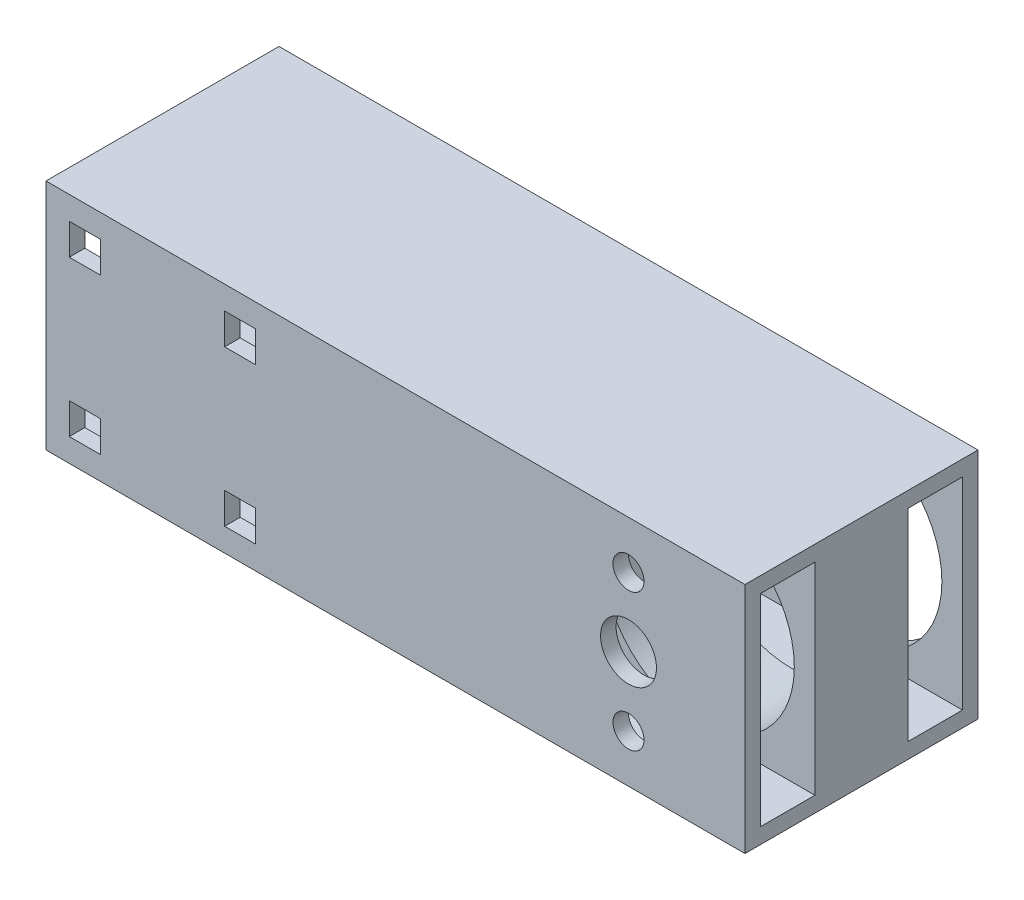
SolidWorks part; units mm, degrees
material "PLA 15%"
ref_plane "Front Plane" through (0, 0, 0) normal (0, 0, 1) x (1, 0, 0)
ref_plane "Top Plane" through (0, 0, 0) normal (0, 1, 0) x (1, 0, 0)
ref_plane "Right Plane" through (0, 0, 0) normal (1, 0, 0) x (0, 0, -1)
sketch "Sketch1" plane through (0, 0, 0) normal (1, 0, 0) x (0, 0, -1)
  line L1 (-15, -15) -> (15, -15)
  line L2 (-15, -15) -> (-15, 15)
  line L3 (-15, 15) -> (15, 15)
  line L4 (15, -15) -> (15, 15)
  line L5 (-15, -15) -> (15, 15) construction
  line L6 (-15, 15) -> (15, -15) construction
  line L11 (-5.1844, 5.1844) -> (5.1844, -5.1844) construction
  line L12 (-5.1844, -5.1844) -> (5.1844, 5.1844) construction
  line L13 (-13, 13) -> (-6, 13)
  line L14 (-13, 13) -> (-13, -13)
  line L15 (-13, -13) -> (-6, -13)
  line L16 (-6, 13) -> (-6, -13)
  line L17 (13, 13) -> (6, 13)
  line L18 (13, 13) -> (13, -13)
  line L19 (13, -13) -> (6, -13)
  line L20 (6, 13) -> (6, -13)
  point P0 (0, 0)
  point P7 (0, 0)
  dimension "D1" = 30
  dimension "D2" = 30
  dimension "D3" = 2
  dimension "D4" = 7
  dimension "D5" = 2
  dimension "D6" = 7
  dimension "D7" = 2
  dimension "D8" = 2
extrude "Boss-Extrude3" add sketch "Sketch1" along normal blind 90
sketch "Sketch6" plane through (0, 0, -15) normal (0, 0, -1) x (-1, 0, 0)
  line L0 (-90, -15) -> (-90, 15) construction
  circle A0 centre (-75, 0) radius 12.35
  dimension "D2" = 24.7
  dimension "D1" = 15
extrude "Cut-Extrude5" cut sketch "Sketch6" against normal blind 23
sketch "Sketch8" plane through (0, 0, 15) normal (0, 0, 1) x (1, 0, 0)
  line L0 (90, 15) -> (90, -15) construction
  circle A0 centre (75, 0) radius 3.6
  circle A1 centre (75, 8.85) radius 2
  circle A2 centre (75, -8.85) radius 2
  dimension "D2" = 7.2
  dimension "D5" = 4
  dimension "D6" = 4
  dimension "D1" = 15
  dimension "D3" = 8.85
  dimension "D4" = 8.85
extrude "Cut-Extrude6" cut sketch "Sketch8" against normal blind 17
sketch "Sketch9" plane through (0, 0, 0) normal (-1, 0, 0) x (0, 0, 1)
  line L0 (-6, 13) -> (6, 13)
  line L1 (-6, -13) -> (6, -13)
  line L2 (-6, 13) -> (-6, -13)
  line L3 (6, 13) -> (6, -13)
extrude "Cut-Extrude7" cut sketch "Sketch9" against normal blind 59
sketch "Sketch10" plane through (0, 0, -15) normal (0, 0, -1) x (-1, 0, 0)
  line L0 (0, 15) -> (-30, 15)
  line L1 (-90, 15) -> (0, 15) construction
  line L2 (-30, 15) -> (-30, -15)
  line L3 (-90, -15) -> (0, -15) construction
  line L4 (-30, -15) -> (0, -15)
  line L5 (-25, 10) -> (0, 10)
  line L6 (0, -15) -> (0, 15) construction
  line L7 (-25, 10) -> (-25, -15)
  line L9 (-3, 8) -> (-7, 8)
  line L10 (-3, 8) -> (-3, 12)
  line L11 (-3, 12) -> (-7, 12)
  line L12 (-7, 8) -> (-7, 12)
  line L13 (-3, 8) -> (-7, 12) construction
  line L14 (-3, 12) -> (-7, 8) construction
  line L15 (-27, 8) -> (-23, 8)
  line L16 (-27, 8) -> (-27, 12)
  line L17 (-27, 12) -> (-23, 12)
  line L18 (-23, 8) -> (-23, 12)
  line L19 (-27, 8) -> (-23, 12) construction
  line L20 (-27, 12) -> (-23, 8) construction
  line L22 (-27, -12) -> (-23, -12)
  line L23 (-27, -12) -> (-27, -8)
  line L24 (-27, -8) -> (-23, -8)
  line L25 (-23, -12) -> (-23, -8)
  line L26 (-27, -12) -> (-23, -8) construction
  line L27 (-27, -8) -> (-23, -12) construction
  line L28 (-3, -12) -> (-7, -12)
  line L29 (-3, -12) -> (-3, -8)
  line L30 (-3, -8) -> (-7, -8)
  line L31 (-7, -12) -> (-7, -8)
  line L32 (-3, -12) -> (-7, -8) construction
  line L33 (-3, -8) -> (-7, -12) construction
  circle A0 centre (-25, 10) radius 2
  circle A1 centre (-5, 10) radius 2
  circle A2 centre (-25, -10) radius 2
  circle A3 centre (-5, -10) radius 2
  dimension "D3" = 4
  dimension "D4" = 5
  dimension "D5" = 4
  dimension "D7" = 4
  dimension "D8" = 4
  dimension "D1" = 5
  dimension "D2" = 5
  dimension "D6" = 5
  dimension "D9" = 4
  dimension "D10" = 4
  dimension "D11" = 4
  dimension "D12" = 4
  dimension "D13" = 4
  dimension "D14" = 20
extrude "Cut-Extrude8" cut sketch "Sketch10" against normal blind 34 contours L17 L18 L15 L16 | L11 L12 L9 L10 | L24 L25 L22 L23 | L30 L31 L28 L29
